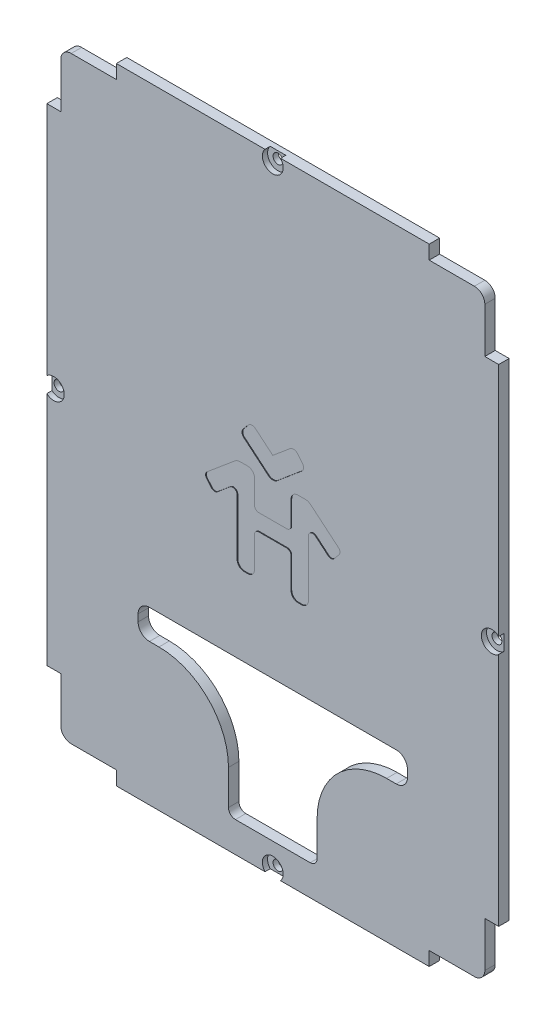
SolidWorks part; units mm, degrees
ref_plane "Спереди" through (0, 0, 0) normal (0, 0, 1) x (1, 0, 0)
ref_plane "Сверху" through (0, 0, 0) normal (0, 1, 0) x (1, 0, 0)
ref_plane "Справа" through (0, 0, 0) normal (1, 0, 0) x (0, 0, -1)
sketch "Эскиз1" plane through (0, 0, 0) normal (0, 0, 1) x (1, 0, 0)
  line L1 (-55, -90) -> (55, -90)
  line L2 (-65, -80) -> (-65, 80)
  line L3 (-55, 90) -> (55, 90)
  line L4 (65, -80) -> (65, 80)
  line L5 (-65, -90) -> (65, 90) construction
  line L6 (-65, 90) -> (65, -90) construction
  arc A0 (-55, 90) -> (-65, 80) centre (-55, 80) ccw
  arc A1 (-55, -90) -> (-65, -80) centre (-55, -80) cw
  arc A2 (55, 90) -> (65, 80) centre (55, 80) cw
  arc A3 (65, -80) -> (55, -90) centre (55, -80) cw
  point P0 (0, 0)
  dimension "D3" = 10
  dimension "D4" = 10
  dimension "D1" = 130
  dimension "D2" = 180
extrude "Бобышка-Вытянуть1" add sketch "Эскиз1" along normal blind 3
sketch "Эскиз2" plane through (0, 0, 0) normal (0, 0, -1) x (-1, 0, 0)
  line L0 (-38.75, -44) -> (-38.75, -46)
  line L1 (-35.5, -49.25) -> (-32.75, -49.25)
  line L2 (-12.75, -69.25) -> (-12.75, -79.25)
  line L3 (-10.75, -81.25) -> (10.75, -81.25)
  line L4 (12.75, -79.25) -> (12.75, -69.25)
  line L5 (32.75, -49.25) -> (35.5, -49.25)
  line L6 (38.75, -46) -> (38.75, -44)
  line L7 (35.5, -40.75) -> (-35.5, -40.75)
  line L8 (-65, -80) -> (-65, 80) construction
  line L9 (65, 80) -> (65, -80) construction
  line L10 (55, -90) -> (-55, -90) construction
  arc A0 (32.75, -49.25) -> (12.75, -69.25) centre (32.75, -69.25) ccw
  arc A1 (-12.75, -69.25) -> (-32.75, -49.25) centre (-32.75, -69.25) ccw
  arc A2 (35.5, -49.25) -> (38.75, -46) centre (35.5, -46) ccw
  arc A3 (38.75, -44) -> (35.5, -40.75) centre (35.5, -44) ccw
  arc A4 (-35.5, -49.25) -> (-38.75, -46) centre (-35.5, -46) cw
  arc A5 (-35.5, -40.75) -> (-38.75, -44) centre (-35.5, -44) ccw
  arc A6 (12.75, -79.25) -> (10.75, -81.25) centre (10.75, -79.25) cw
  arc A7 (-10.75, -81.25) -> (-12.75, -79.25) centre (-10.75, -79.25) cw
  point P16 (12.75, -49.25)
  point P21 (38.75, -49.25)
  point P24 (38.75, -40.75)
  point P31 (12.75, -81.25)
  point P34 (-12.75, -81.25)
  dimension "D7" = 20
  dimension "D8" = 3.25
  dimension "D9" = 2
  dimension "D1" = 26.25
  dimension "D2" = 26.25
  dimension "D3" = 49.25
  dimension "D4" = 8.5
  dimension "D5" = 25.5
  dimension "D6" = 32
extrude "Вырез-Вытянуть1" cut sketch "Эскиз2" against normal blind 10
sketch "Эскиз3" plane through (0, 0, 3) normal (0, 0, 1) x (1, 0, 0)
  line L0 (-63, -940.9285) -> (-63, 49059.0715) construction
  line L1 (63, -944.6511) -> (63, 49055.3489) construction
  line L2 (-1032.3277, 88) -> (48967.6723, 88) construction
  line L3 (-1028.801, -88) -> (48971.199, -88) construction
  line L4 (-55, -90) -> (55, -90) construction
  line L6 (-65, 80) -> (-65, -80) construction
  line L7 (65, -80) -> (65, 80) construction
  line L8 (55, 90) -> (-55, 90) construction
  line L9 (0, -925) -> (0, 49075) construction
  line L10 (-1052.5, 0) -> (48947.5, 0) construction
  circle A1 centre (0, 88) radius 3
  circle A3 centre (63, 0) radius 3
  circle A5 centre (0, -88) radius 3
  circle A7 centre (-63, 0) radius 3
  point P19 (0, 90)
  point P22 (-65, 0)
  dimension "D5" = 6
  dimension "D1" = 2
  dimension "D2" = 2
  dimension "D3" = 2
  dimension "D4" = 2
extrude "Вырез-Вытянуть2" cut sketch "Эскиз3" against normal blind 1.5
sketch "Эскиз4" plane through (0, 0, 1.5) normal (0, 0, 1) x (1, 0, 0)
  circle A1 centre (0, 88) radius 1.425
  circle A3 centre (63, 0) radius 1.425
  circle A5 centre (0, -88) radius 1.425
  circle A7 centre (-63, 0) radius 1.425
  dimension "D1" = 2.85
extrude "Вырез-Вытянуть3" cut sketch "Эскиз4" against normal blind 2
sketch "Эскиз5" plane through (0, 0, 3) normal (0, 0, 1) x (1, 0, 0)
  line L0 (-10.25, -0.0911) -> (-10.25, -16.2185)
  line L1 (-8.25, -18.2185) -> (-7.25, -18.2185)
  line L2 (-5.25, -16.2185) -> (-5.25, -7.4685)
  line L3 (-4, -6.2185) -> (4, -6.2185)
  line L4 (-9.3401, 8.5815) -> (-7.25, 8.5815)
  line L5 (-5.25, 6.5815) -> (-5.25, -0.1685)
  line L6 (0, -1000.6685) -> (0, 48999.3315) construction
  line L7 (-4, -1.4185) -> (4, -1.4185)
  line L8 (-10.947, 7.9966) -> (-18.868, 1.3501)
  line L9 (-19.0221, -0.4109) -> (-17.6786, -2.012)
  line L10 (-15.9176, -2.1661) -> (-12.3035, 0.8665)
  line L11 (15.9176, -2.1661) -> (12.3035, 0.8665)
  line L12 (19.0221, -0.4109) -> (17.6786, -2.012)
  line L13 (10.947, 7.9966) -> (18.868, 1.3501)
  line L14 (5.25, 6.5815) -> (5.25, -0.1685)
  line L15 (9.3401, 8.5815) -> (7.25, 8.5815)
  line L16 (5.25, -16.2185) -> (5.25, -7.4685)
  line L17 (8.25, -18.2185) -> (7.25, -18.2185)
  line L18 (10.25, -0.0911) -> (10.25, -16.2185)
  line L19 (0, 14.8585) -> (-4.9795, 19.0368)
  line L20 (-7.0927, 18.8519) -> (-8.4839, 17.194)
  line L21 (-8.299, 15.0808) -> (-1.2856, 9.1958)
  line L22 (8.299, 15.0808) -> (1.2856, 9.1958)
  line L23 (0, 14.8585) -> (4.9795, 19.0368)
  line L24 (7.0927, 18.8519) -> (8.4839, 17.194)
  arc A0 (-10.25, -16.2185) -> (-8.25, -18.2185) centre (-8.25, -16.2185) ccw
  arc A1 (-7.25, -18.2185) -> (-5.25, -16.2185) centre (-7.25, -16.2185) ccw
  arc A2 (-5.25, 6.5815) -> (-7.25, 8.5815) centre (-7.25, 6.5815) ccw
  arc A3 (-9.3401, 8.5815) -> (-10.947, 7.9966) centre (-9.3401, 6.0815) ccw
  arc A4 (-4, -6.2185) -> (-5.25, -7.4685) centre (-4, -7.4685) ccw
  arc A5 (-4, -1.4185) -> (-5.25, -0.1685) centre (-4, -0.1685) cw
  arc A6 (-10.25, -0.0911) -> (-12.3035, 0.8665) centre (-11.5, -0.0911) ccw
  arc A7 (-15.9176, -2.1661) -> (-17.6786, -2.012) centre (-16.721, -1.2085) cw
  arc A8 (-18.868, 1.3501) -> (-19.0221, -0.4109) centre (-18.0645, 0.3926) ccw
  arc A9 (18.868, 1.3501) -> (19.0221, -0.4109) centre (18.0645, 0.3926) cw
  arc A10 (15.9176, -2.1661) -> (17.6786, -2.012) centre (16.721, -1.2085) ccw
  arc A11 (10.25, -0.0911) -> (12.3035, 0.8665) centre (11.5, -0.0911) cw
  arc A12 (4, -1.4185) -> (5.25, -0.1685) centre (4, -0.1685) ccw
  arc A13 (4, -6.2185) -> (5.25, -7.4685) centre (4, -7.4685) cw
  arc A14 (9.3401, 8.5815) -> (10.947, 7.9966) centre (9.3401, 6.0815) cw
  arc A15 (5.25, 6.5815) -> (7.25, 8.5815) centre (7.25, 6.5815) cw
  arc A16 (7.25, -18.2185) -> (5.25, -16.2185) centre (7.25, -16.2185) cw
  arc A17 (10.25, -16.2185) -> (8.25, -18.2185) centre (8.25, -16.2185) cw
  arc A18 (-8.299, 15.0808) -> (-8.4839, 17.194) centre (-7.3348, 16.2298) cw
  arc A19 (-4.9795, 19.0368) -> (-7.0927, 18.8519) centre (-5.9437, 17.8877) ccw
  arc A20 (4.9795, 19.0368) -> (7.0927, 18.8519) centre (5.9437, 17.8877) cw
  arc A21 (8.299, 15.0808) -> (8.4839, 17.194) centre (7.3348, 16.2298) ccw
  arc A22 (1.2856, 9.1958) -> (-1.2856, 9.1958) centre (0, 10.7279) cw
  point P35 (0, -6.2185)
  point P36 (0, -1.4185)
  point P61 (19.57, 0.5466)
  point P62 (4.9945, -1.4185)
  point P63 (4.9945, -6.2185)
  point P64 (9.9945, 8.5815)
  point P65 (4.9945, 8.5815)
  point P66 (4.9945, -18.2185)
  point P67 (9.9945, -18.2185)
  point P79 (5.7231, 19.8752)
  point P80 (8.937, 16.0449)
  dimension "D3" = 2
  dimension "D4" = 2.5
  dimension "D6" = 1.5
  dimension "D7" = 2
  dimension "D8" = 1.25
  dimension "D1" = 5.25
  dimension "D2" = 50
  dimension "D5" = 50
extrude "Вырез-Вытянуть4" cut sketch "Эскиз5" against normal blind 0.2
sketch "Эскиз8" plane through (0, 0, 3) normal (0, 0, 1) x (1, 0, 0)
  line L0 (-55, 90) -> (-45, 90)
  line L1 (-2.2361, 90) -> (-55, 90) construction
  line L2 (-45, 90) -> (-45, 86)
  line L3 (-45, 86) -> (-58, 86)
  line L5 (-61, 83) -> (-61, 70)
  line L6 (-61, 70) -> (-65, 70)
  line L7 (-65, 80) -> (-65, 2.2361) construction
  line L8 (-65, 70) -> (-65, 80)
  line L9 (-1000, 0) -> (49000, 0) construction
  line L10 (0, -1000) -> (0, 49000) construction
  line L11 (65, 70) -> (65, 80)
  line L12 (61, 70) -> (65, 70)
  line L13 (61, 83) -> (61, 70)
  line L14 (45, 86) -> (58, 86)
  line L15 (45, 90) -> (45, 86)
  line L16 (55, 90) -> (45, 90)
  line L17 (55, -90) -> (45, -90)
  line L18 (45, -90) -> (45, -86)
  line L19 (45, -86) -> (58, -86)
  line L20 (61, -83) -> (61, -70)
  line L21 (61, -70) -> (65, -70)
  line L22 (65, -70) -> (65, -80)
  line L23 (-65, -70) -> (-65, -80)
  line L24 (-61, -70) -> (-65, -70)
  line L25 (-61, -83) -> (-61, -70)
  line L26 (-45, -86) -> (-58, -86)
  line L27 (-45, -90) -> (-45, -86)
  line L28 (-55, -90) -> (-45, -90)
  arc A0 (-55, 90) -> (-65, 80) centre (-55, 80) ccw construction
  arc A1 (-55, 90) -> (-65, 80) centre (-55, 80) ccw
  arc A2 (-61, 83) -> (-58, 86) centre (-58, 83) cw
  arc A3 (61, 83) -> (58, 86) centre (58, 83) ccw
  arc A4 (55, 90) -> (65, 80) centre (55, 80) cw
  arc A5 (55, -90) -> (65, -80) centre (55, -80) ccw
  arc A6 (61, -83) -> (58, -86) centre (58, -83) cw
  arc A7 (-61, -83) -> (-58, -86) centre (-58, -83) ccw
  arc A8 (-55, -90) -> (-65, -80) centre (-55, -80) cw
  dimension "D3" = 3
  dimension "D1" = 10
  dimension "D2" = 4
extrude "Вырез-Вытянуть5" cut sketch "Эскиз8" against normal blind 10
